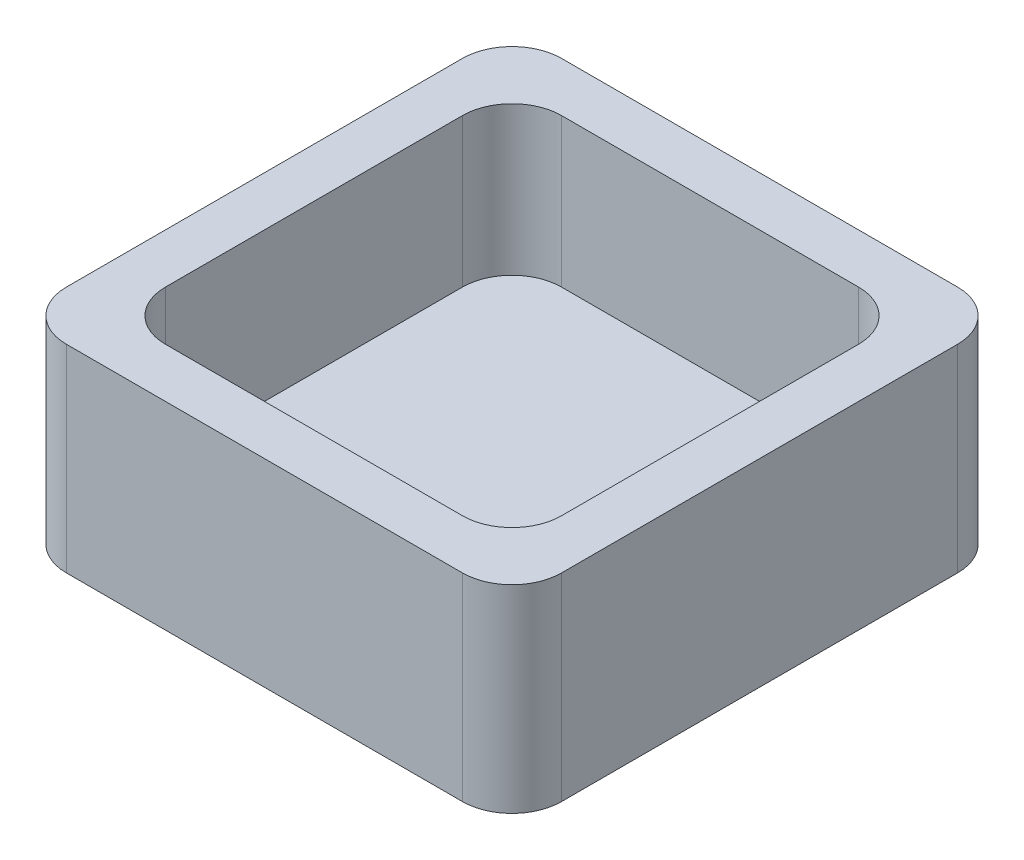
SolidWorks part; units mm, degrees
ref_plane "Front Plane" through (0, 0, 0) normal (0, 0, 1) x (1, 0, 0)
ref_plane "Top Plane" through (0, 0, 0) normal (0, 1, 0) x (1, 0, 0)
ref_plane "Right Plane" through (0, 0, 0) normal (1, 0, 0) x (0, 0, -1)
sketch "Sketch1" plane through (0, 0, 0) normal (0, 1, 0) x (1, 0, 0)
  line L1 (50, 50) -> (-50, 50)
  line L2 (50, 50) -> (50, -50)
  line L3 (50, -50) -> (-50, -50)
  line L4 (-50, 50) -> (-50, -50)
  line L5 (50, 50) -> (-50, -50) construction
  line L6 (50, -50) -> (-50, 50) construction
  point P0 (0, 0)
  dimension "D1" = 100
  dimension "D2" = 100
extrude "Boss-Extrude1" add sketch "Sketch1" along normal blind 40
sketch "Sketch2" plane through (0, 40, 0) normal (0, 1, 0) x (1, 0, 0)
  line L1 (40, 40) -> (-40, 40)
  line L2 (40, 40) -> (40, -40)
  line L3 (40, -40) -> (-40, -40)
  line L4 (-40, 40) -> (-40, -40)
  line L5 (40, 40) -> (-40, -40) construction
  line L6 (40, -40) -> (-40, 40) construction
  point P0 (0, 0)
  dimension "D1" = 80
  dimension "D2" = 80
extrude "Cut-Extrude1" cut sketch "Sketch2" against normal blind 30
sketch "Sketch3" plane through (0, 0, 0) normal (0, -1, 0) x (1, 0, 0)
  line L1 (40, 40) -> (-40, 40)
  line L2 (40, 40) -> (40, -40)
  line L3 (40, -40) -> (-40, -40)
  line L4 (-40, 40) -> (-40, -40)
  line L5 (40, 40) -> (-40, -40) construction
  line L6 (40, -40) -> (-40, 40) construction
  point P0 (0, 0)
  dimension "D1" = 80
  dimension "D2" = 80
extrude "Boss-Extrude2" add sketch "Sketch3" along normal blind 5
fillet "Fillet2" radius 10 8 edges at (40, 25, 40) (40, 25, -40) (-40, 25, -40) (-40, 25, 40) (50, 20, 50) (50, 20, -50) (-50, 20, -50) (-50, 20, 50)
fillet "Fillet4" radius 7 4 edges at (40, -2.5, -40) (40, -2.5, 40) (-40, -2.5, 40) (-40, -2.5, -40)
fillet "Fillet5" radius 7 8 edges at (-37.9497, 0, 37.9497) (0, 0, 40) (37.9497, 0, 37.9497) (40, 0, 0) (37.9497, 0, -37.9497) (0, 0, -40) (-37.9497, 0, -37.9497) (-40, 0, 0)
